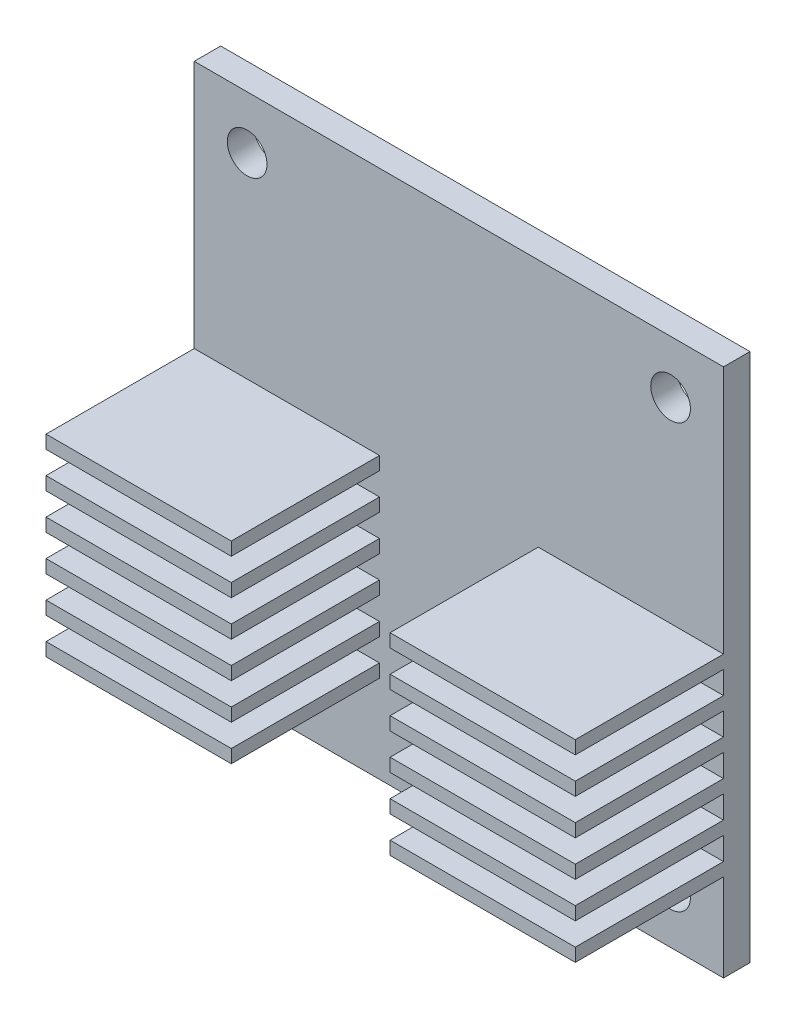
SolidWorks part; units mm, degrees
ref_plane "Front Plane" through (0, 0, 0) normal (0, 0, 1) x (1, 0, 0)
ref_plane "Top Plane" through (0, 0, 0) normal (0, 1, 0) x (1, 0, 0)
ref_plane "Right Plane" through (0, 0, 0) normal (1, 0, 0) x (0, 0, -1)
sketch "Sketch1" plane through (0, 0, 0) normal (0, 0, 1) x (1, 0, 0)
  line L0 (41, 4.4837) -> (27, 4.4837)
  line L1 (41, 2.4837) -> (1, 2.4837)
  line L2 (41, 2.4837) -> (41, 42.4837)
  line L3 (41, 42.4837) -> (1, 42.4837)
  line L4 (1, 2.4837) -> (1, 42.4837)
  line L5 (21, 40.4837) -> (21, 4.4837) construction
  line L6 (41, 21.7785) -> (27, 21.7785) construction
  line L7 (41, 4.4837) -> (41, 40.4837)
  line L8 (27, 4.4837) -> (27, 40.4837)
  line L9 (15, 4.4837) -> (15, 40.4837)
  line L10 (1, 4.4837) -> (1, 40.4837)
  line L11 (25, 4.4837) -> (25, 40.4837)
  line L12 (17, 4.4837) -> (17, 40.4837)
  line L13 (41, 40.4837) -> (27, 40.4837)
  line L14 (41, 5.4837) -> (27, 5.4837)
  line L15 (41, 6.389) -> (27, 6.389)
  line L16 (41, 7.2943) -> (27, 7.2943)
  line L17 (41, 8.1995) -> (27, 8.1995)
  line L18 (41, 9.1048) -> (27, 9.1048)
  line L19 (41, 10.01) -> (27, 10.01)
  line L20 (41, 10.9153) -> (27, 10.9153)
  line L21 (41, 11.8206) -> (27, 11.8206)
  line L22 (41, 12.7258) -> (27, 12.7258)
  line L23 (41, 13.6311) -> (27, 13.6311)
  line L24 (41, 14.5364) -> (27, 14.5364)
  line L25 (41, 15.4416) -> (27, 15.4416)
  line L26 (41, 16.3469) -> (27, 16.3469)
  line L27 (41, 17.2522) -> (27, 17.2522)
  line L28 (41, 18.1574) -> (27, 18.1574)
  line L29 (41, 19.0627) -> (27, 19.0627)
  line L30 (41, 19.9679) -> (27, 19.9679)
  line L31 (41, 20.8732) -> (27, 20.8732)
  line L32 (41, 21.7785) -> (27, 21.7785)
  line L33 (41, 22.6837) -> (27, 22.6837)
  line L34 (41, 23.589) -> (27, 23.589)
  line L35 (41, 24.4943) -> (27, 24.4943)
  line L36 (41, 25.3995) -> (27, 25.3995)
  line L37 (41, 26.3048) -> (27, 26.3048)
  line L38 (41, 27.21) -> (27, 27.21)
  line L39 (41, 28.1153) -> (27, 28.1153)
  line L40 (41, 29.0206) -> (27, 29.0206)
  line L41 (41, 29.9258) -> (27, 29.9258)
  line L42 (41, 30.8311) -> (27, 30.8311)
  line L43 (41, 31.7364) -> (27, 31.7364)
  line L44 (41, 32.6416) -> (27, 32.6416)
  line L45 (41, 33.5469) -> (27, 33.5469)
  line L46 (41, 34.4522) -> (27, 34.4522)
  line L47 (41, 35.3574) -> (27, 35.3574)
  line L48 (41, 36.2627) -> (27, 36.2627)
  line L49 (41, 37.1679) -> (27, 37.1679)
  line L50 (41, 38.0732) -> (27, 38.0732)
  line L51 (46.6374, 3.6837) -> (46.6374, 4.6837) construction
  line L52 (45.6374, 5.4837) -> (-11.288, 5.4837) construction
  line L53 (45.6374, 4.4837) -> (-11.288, 4.4837) construction
  line L54 (25, 4.4837) -> (17, 4.4837)
  line L55 (25, 5.4837) -> (17, 5.4837)
  line L56 (25, 6.389) -> (17, 6.389)
  line L57 (25, 7.2943) -> (17, 7.2943)
  line L58 (25, 8.1995) -> (17, 8.1995)
  line L59 (25, 9.1048) -> (17, 9.1048)
  line L60 (25, 10.01) -> (17, 10.01)
  line L61 (25, 10.9153) -> (17, 10.9153)
  line L62 (25, 11.8206) -> (17, 11.8206)
  line L63 (25, 12.7258) -> (17, 12.7258)
  line L64 (25, 13.6311) -> (17, 13.6311)
  line L65 (25, 14.5364) -> (17, 14.5364)
  line L66 (25, 15.4416) -> (17, 15.4416)
  line L67 (25, 16.3469) -> (17, 16.3469)
  line L68 (25, 17.2522) -> (17, 17.2522)
  line L69 (25, 18.1574) -> (17, 18.1574)
  line L70 (25, 19.0627) -> (17, 19.0627)
  line L71 (25, 19.9679) -> (17, 19.9679)
  line L72 (25, 20.8732) -> (17, 20.8732)
  line L73 (25, 21.7785) -> (17, 21.7785) construction
  line L74 (25, 21.7785) -> (17, 21.7785)
  line L75 (25, 22.6837) -> (17, 22.6837)
  line L76 (25, 23.589) -> (17, 23.589)
  line L77 (25, 24.4943) -> (17, 24.4943)
  line L78 (25, 25.3995) -> (17, 25.3995)
  line L79 (25, 26.3048) -> (17, 26.3048)
  line L80 (25, 27.21) -> (17, 27.21)
  line L81 (25, 28.1153) -> (17, 28.1153)
  line L82 (25, 29.0206) -> (17, 29.0206)
  line L83 (25, 29.9258) -> (17, 29.9258)
  line L84 (25, 30.8311) -> (17, 30.8311)
  line L85 (25, 31.7364) -> (17, 31.7364)
  line L86 (25, 32.6416) -> (17, 32.6416)
  line L87 (25, 33.5469) -> (17, 33.5469)
  line L88 (25, 34.4522) -> (17, 34.4522)
  line L89 (25, 35.3574) -> (17, 35.3574)
  line L90 (25, 36.2627) -> (17, 36.2627)
  line L91 (25, 37.1679) -> (17, 37.1679)
  line L92 (25, 38.0732) -> (17, 38.0732)
  line L93 (25, 40.4837) -> (17, 40.4837)
  line L94 (15, 4.4837) -> (1, 4.4837)
  line L95 (15, 5.4837) -> (1, 5.4837)
  line L96 (15, 6.389) -> (1, 6.389)
  line L97 (15, 7.2943) -> (1, 7.2943)
  line L98 (15, 8.1995) -> (1, 8.1995)
  line L99 (15, 9.1048) -> (1, 9.1048)
  line L100 (15, 10.01) -> (1, 10.01)
  line L101 (15, 10.9153) -> (1, 10.9153)
  line L102 (15, 11.8206) -> (1, 11.8206)
  line L103 (15, 12.7258) -> (1, 12.7258)
  line L104 (15, 13.6311) -> (1, 13.6311)
  line L105 (15, 14.5364) -> (1, 14.5364)
  line L106 (15, 15.4416) -> (1, 15.4416)
  line L107 (15, 16.3469) -> (1, 16.3469)
  line L108 (15, 17.2522) -> (1, 17.2522)
  line L109 (15, 18.1574) -> (1, 18.1574)
  line L110 (15, 19.0627) -> (1, 19.0627)
  line L111 (15, 19.9679) -> (1, 19.9679)
  line L112 (15, 20.8732) -> (1, 20.8732)
  line L113 (15, 21.7785) -> (1, 21.7785) construction
  line L114 (15, 21.7785) -> (1, 21.7785)
  line L115 (15, 22.6837) -> (1, 22.6837)
  line L116 (15, 23.589) -> (1, 23.589)
  line L117 (15, 24.4943) -> (1, 24.4943)
  line L118 (15, 25.3995) -> (1, 25.3995)
  line L119 (15, 26.3048) -> (1, 26.3048)
  line L120 (15, 27.21) -> (1, 27.21)
  line L121 (15, 28.1153) -> (1, 28.1153)
  line L122 (15, 29.0206) -> (1, 29.0206)
  line L123 (15, 29.9258) -> (1, 29.9258)
  line L124 (15, 30.8311) -> (1, 30.8311)
  line L125 (15, 31.7364) -> (1, 31.7364)
  line L126 (15, 32.6416) -> (1, 32.6416)
  line L127 (15, 33.5469) -> (1, 33.5469)
  line L128 (15, 34.4522) -> (1, 34.4522)
  line L129 (15, 35.3574) -> (1, 35.3574)
  line L130 (15, 36.2627) -> (1, 36.2627)
  line L131 (15, 37.1679) -> (1, 37.1679)
  line L132 (15, 38.0732) -> (1, 38.0732)
  line L133 (15, 40.4837) -> (1, 40.4837)
  point P48 (21, 21.7785)
  dimension "D1" = 2
  dimension "D2" = 2
  dimension "D3" = 0
  dimension "D4" = 0
  dimension "D5" = 2
  dimension "D6" = 2
  dimension "D7" = 14
  dimension "D8" = 14
  dimension "D10" = 1
  dimension "D9" = 1
extrude "Boss-Extrude1" add sketch "Sketch1" along normal blind 2 contours L1 L4 L3 L2
extrude "Extrude-Thin1" add sketch "Sketch1<3>" along normal blind 11.2 from surface thin contours L33 | L30 | L111 | L115 | L27 | L24 | L108 | L105 | L21 | L102 | L18 | L99 starting at face at (21, 22.4837, 2) thin type one direction wall 1
sketch "Sketch1<3>" plane through (0, 0, 0) normal (0, 0, 1) x (1, 0, 0) same geometry as "Sketch1"
sketch "Sketch3" plane through (0, 0, 0) normal (0, 0, -1) x (-1, 0, 0)
  line L1 (-21, 2.4837) -> (-21, 42.4837) construction
  line L2 (-5, 38.4837) -> (-37, 38.4837) construction
  line L3 (-5, 38.4837) -> (-5, 6.4837) construction
  line L4 (-5, 6.4837) -> (-37, 6.4837) construction
  line L5 (-37, 38.4837) -> (-37, 6.4837) construction
  line L6 (-21, 6.4837) -> (-21, 38.4837) construction
  line L7 (-5, 22.4837) -> (-37, 22.4837) construction
  line L8 (-41, 2.4837) -> (-1, 2.4837) construction
  line L9 (-41, 42.4837) -> (-1, 42.4837) construction
  line L10 (-41, 22.4837) -> (-1, 22.4837) construction
  line L11 (-41, 2.4837) -> (-41, 42.4837) construction
  line L12 (-1, 2.4837) -> (-1, 42.4837) construction
  circle A0 centre (-37, 6.4837) radius 1.5
  circle A1 centre (-5, 6.4837) radius 1.5
  circle A2 centre (-5, 38.4837) radius 1.5
  circle A3 centre (-37, 38.4837) radius 1.5
  point P141 (-21, 22.4837)
  dimension "D1" = 3
  dimension "D4" = 3
  dimension "D5" = 3
  dimension "D6" = 3
  dimension "D2" = 32
  dimension "D3" = 32
extrude "Cut-Extrude1" cut sketch "Sketch3" along direction (0, 0, 1) on the side against the normal up to vertex (2 mm away) from vertex contours A0 up to point (1, 2.4837, 2) starting at point (1, 2.4837, 0)
pattern_linear "LPattern1" count 2 spacing 32 along (-1, 0, 0) count 2 spacing 32 along (0, 1, 0) of "Cut-Extrude1"
